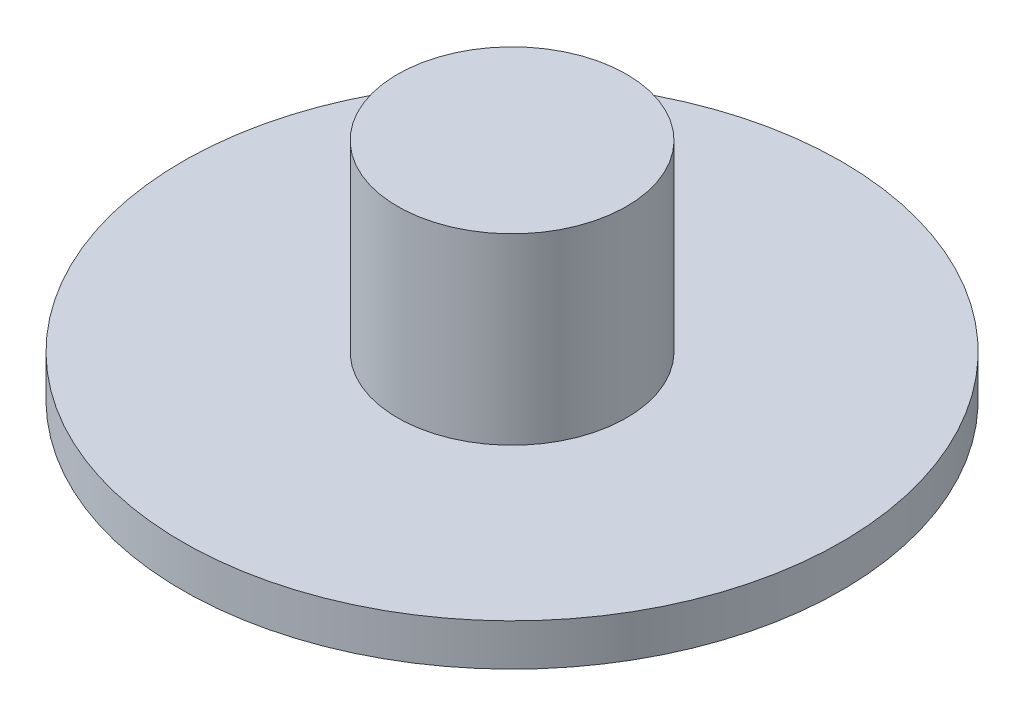
SolidWorks part; units mm, degrees
material "6061-T6 (SS)"
ref_plane "Front Plane" through (0, 0, 0) normal (0, 0, 1) x (1, 0, 0)
ref_plane "Top Plane" through (0, 0, 0) normal (0, 1, 0) x (1, 0, 0)
ref_plane "Right Plane" through (0, 0, 0) normal (1, 0, 0) x (0, 0, -1)
sketch "Sketch1" plane through (0, 0, 0) normal (1, 0, 0) x (0, 0, -1)
  line L0 (-20, 0) -> (0, 0)
  line L2 (0, 0) -> (0, 13.6525)
  line L3 (0, 13.6525) -> (-6.95, 13.6525)
  line L4 (-6.95, 2.54) -> (-6.95, 13.6525)
  line L9 (-6.95, 2.54) -> (-20, 2.54)
  line L10 (-20, 0) -> (-20, 2.54)
  point P0 (0, 0)
  dimension "D1" = 20
  dimension "D2" = 6.95
  dimension "D3" = 11.1125
  dimension "D4" = 2.54
revolve "Revolve1" add sketch "Sketch1" angle 360 about L2
